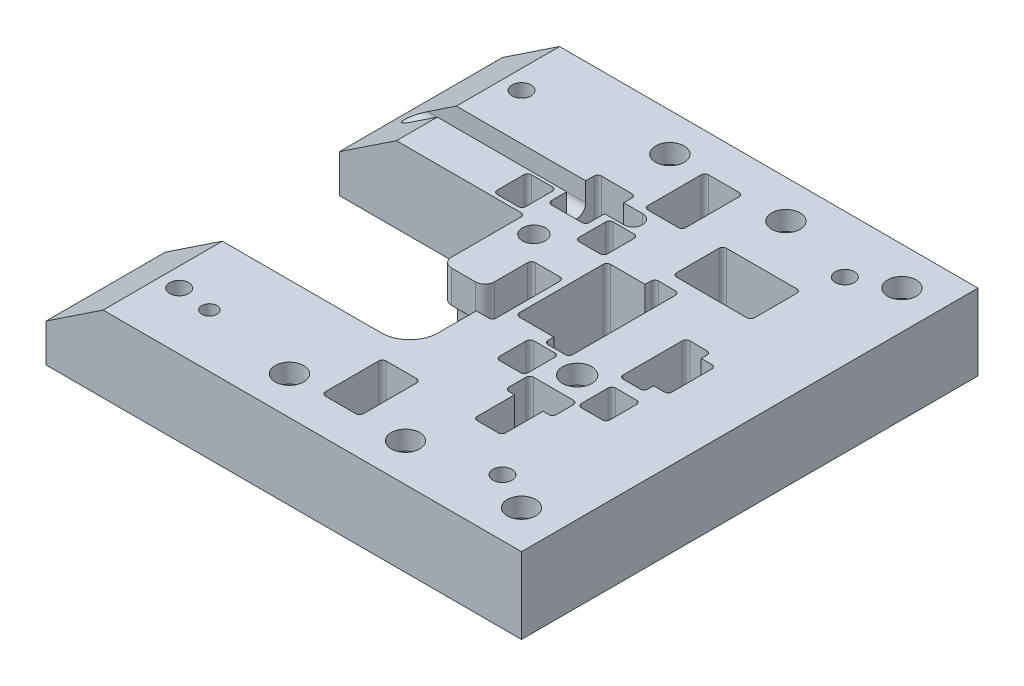
SolidWorks part; units mm, degrees
material "K110"
ref_plane "Front Plane" through (0, 0, 0) normal (0, 0, 1) x (1, 0, 0)
ref_plane "Top Plane" through (0, 0, 0) normal (0, 1, 0) x (1, 0, 0)
ref_plane "Right Plane" through (0, 0, 0) normal (1, 0, 0) x (0, 0, -1)
sketch "Sketch1" plane through (0, 0, 0) normal (0, 1, 0) x (1, 0, 0)
  line L1 (-125, -120) -> (125, -120)
  line L2 (-125, -120) -> (-125, 120)
  line L3 (-125, 120) -> (125, 120)
  line L4 (125, -120) -> (125, 120)
  line L5 (-125, -120) -> (125, 120) construction
  line L6 (-125, 120) -> (125, -120) construction
  point P0 (0, 0)
  dimension "D1" = 240
  dimension "D2" = 250
extrude "Boss-Extrude1" add sketch "Sketch1" along normal blind 40
sketch "Sketch2" plane through (0, 40, 0) normal (0, 1, 0) x (1, 0, 0)
  line L0 (40.25, 55.73) -> (78.25, 55.73) construction
  line L1 (38.75, 32.73) -> (38.75, -12.27) construction
  line L2 (81.25, 13.73) -> (81.25, -8.27) construction
  line L3 (53.25, -47.4) -> (65.25, -47.4) construction
  line L4 (40.25, 55.73) -> (78.25, 55.73)
  line L5 (38.75, 32.73) -> (38.75, -12.27)
  line L6 (81.25, 13.73) -> (81.25, -8.27)
  line L7 (53.25, -47.4) -> (65.25, -47.4)
sketch "Sketch3" plane through (0, 40, 0) normal (0, 1, 0) x (1, 0, 0)
  line L0 (53.25, -47.4) -> (65.25, -47.4) construction
  line L1 (51.75, -72.03) -> (66.75, -72.03)
  line L2 (51.75, -72.03) -> (51.75, -50.4)
  line L3 (46.75, -37.4) -> (71.75, -37.4)
  line L4 (66.75, -72.03) -> (66.75, -50.4)
  line L8 (59.25, -37.4) -> (59.25, -72.03) construction
  line L9 (59.25, 69.53) -> (59.25, -69.53) construction
  line L11 (66.75, -50.4) -> (71.75, -50.4)
  line L12 (71.75, -50.4) -> (71.75, -37.4)
  line L13 (51.75, -50.4) -> (46.75, -50.4)
  line L14 (46.75, -50.4) -> (46.75, -37.4)
  line L15 (89.38, -69.53) -> (18.13, -69.53) construction
  dimension "D1" = 10
  dimension "D2" = 15
  dimension "D3" = 3
  dimension "D4" = 25
  dimension "D5" = 2.5
extrude "Cut-Extrude2" cut sketch "Sketch3" against normal up to next contours L3 L12 L11 L4 L1 L2 L13 L14
fillet "Fillet3" radius 2 6 edges at (66.75, 20, 72.03) (51.75, 20, 72.03) (71.75, 20, 50.4) (46.75, 20, 50.4) (71.75, 20, 37.4) (46.75, 20, 37.4)
sketch "Sketch4" plane through (0, 40, 0) normal (0, 1, 0) x (1, 0, 0)
  line L0 (71.25, -14.77) -> (84.25, -14.77)
  line L5 (84.25, -14.77) -> (84.25, -9.77)
  line L6 (87.38, 13.73) -> (81.25, 13.73) construction
  line L7 (89.38, 69.53) -> (89.38, -69.53) construction
  line L8 (89.38, 2.73) -> (51.7072, 2.73) construction
  line L9 (89.38, -6.27) -> (89.38, 11.73) construction
  line L10 (84.25, -9.77) -> (91.88, -9.77)
  line L11 (91.88, -9.77) -> (91.88, 15.23)
  line L13 (91.88, 15.23) -> (84.25, 15.23)
  line L14 (84.25, 15.23) -> (84.25, 20.23)
  line L15 (84.25, 20.23) -> (71.25, 20.23)
  line L16 (71.25, 20.23) -> (71.25, -14.77)
  line L17 (81.25, 13.73) -> (81.25, -8.27) construction
  dimension "D1" = 1.5
  dimension "D2" = 5
  dimension "D3" = 2.5
  dimension "D4" = 10
  dimension "D5" = 3
extrude "Cut-Extrude3" cut sketch "Sketch4" against normal up to next
fillet "Fillet4" radius 2 6 edges at (91.88, 20, 9.77) (91.88, 20, -15.23) (84.25, 20, -20.23) (71.25, 20, -20.23) (71.25, 20, 14.77) (84.25, 20, 14.77)
sketch "Sketch5" plane through (0, 40, 0) normal (0, 1, 0) x (1, 0, 0)
  line L0 (15.63, -13.77) -> (35.75, -13.77)
  line L2 (35.75, -18.77) -> (48.75, -18.77)
  line L3 (48.75, -18.77) -> (48.75, 39.23)
  line L4 (48.75, 39.23) -> (35.75, 39.23)
  line L5 (35.75, 39.23) -> (35.75, 34.23)
  line L6 (35.75, 34.23) -> (15.63, 34.23)
  line L7 (15.63, 34.23) -> (15.63, -13.77)
  line L8 (38.75, 32.73) -> (38.75, -12.27) construction
  line L9 (18.13, 69.53) -> (18.13, -69.53) construction
  line L10 (18.13, 10.23) -> (48.75, 10.23) construction
  line L11 (18.13, 26.73) -> (18.13, -6.27) construction
  line L12 (35.75, -18.77) -> (35.75, -13.77)
  line L13 (24.13, -12.27) -> (38.75, -12.27) construction
  line L17 (5, -8.27) -> (5, 13.73) construction
  line L18 (5, 2.73) -> (-15, 2.73) construction
  dimension "D1" = 3
  dimension "D2" = 10
  dimension "D3" = 2.5
  dimension "D4" = 1.5
  dimension "D5" = 5
extrude "Cut-Extrude4" cut sketch "Sketch5" against normal up to next
fillet "Fillet5" radius 2 6 edges at (48.75, 20, -39.23) (35.75, 20, 18.77) (48.75, 20, 18.77) (15.63, 20, 13.77) (35.75, 20, -39.23) (15.63, 20, -34.23)
sketch "Sketch6" plane through (0, 40, 0) normal (0, 1, 0) x (1, 0, 0)
  line L0 (38.75, 72.03) -> (38.75, 45.73)
  line L3 (38.75, 45.73) -> (79.75, 45.73)
  line L6 (79.75, 45.73) -> (79.75, 72.03)
  line L7 (79.75, 72.03) -> (38.75, 72.03)
  line L8 (59.25, 69.53) -> (59.25, 45.73) construction
  line L9 (59.25, 69.53) -> (59.25, -69.53) construction
  line L10 (89.38, 69.53) -> (18.13, 69.53) construction
  line L12 (40.25, 55.73) -> (78.25, 55.73) construction
  dimension "D1" = 2.5
  dimension "D2" = 41
  dimension "D5" = 10
extrude "Cut-Extrude5" cut sketch "Sketch6" against normal up to next
fillet "Fillet6" radius 2 4 edges at (38.75, 20, -72.03) (79.75, 20, -72.03) (38.75, 20, -45.73) (79.75, 20, -45.73)
sketch "Sketch7" plane through (0, 40, 0) normal (0, 1, 0) x (1, 0, 0)
  line L0 (80.75, -29.77) -> (80.75, -32.27) construction
  line L3 (83.25, -29.77) -> (78.25, -29.77) construction
  line L4 (83.25, -27.27) -> (83.25, -32.27) construction
  line L5 (78.25, -11.27) -> (78.25, -38.4) construction
  line L7 (86.25, -20.77) -> (75.25, -20.77)
  line L8 (88.25, -22.77) -> (88.25, -36.77)
  line L9 (86.25, -38.77) -> (75.25, -38.77)
  line L10 (73.25, -22.77) -> (73.25, -36.77)
  arc A2 (75.25, -38.77) -> (73.25, -36.77) centre (75.25, -36.77) cw
  arc A3 (88.25, -36.77) -> (86.25, -38.77) centre (86.25, -36.77) cw
  arc A4 (86.25, -20.77) -> (88.25, -22.77) centre (86.25, -22.77) cw
  arc A5 (75.25, -20.77) -> (73.25, -22.77) centre (75.25, -22.77) ccw
  point P14 (73.25, -38.77)
  point P17 (88.25, -38.77)
  point P20 (88.25, -20.77)
  dimension "D4" = 2
  dimension "D1" = 2.5
  dimension "D2" = 18
  dimension "D3" = 15
  dimension "D5" = 9
extrude "Cut-Extrude6" cut sketch "Sketch7" against normal up to next
sketch "Sketch8" plane through (0, 40, 0) normal (0, 1, 0) x (1, 0, 0)
  line L0 (35.25, -29.77) -> (40.25, -29.77) construction
  line L3 (35.25, -32.27) -> (35.25, -27.27) construction
  line L4 (86.25, -20.77) -> (75.25, -20.77) construction
  line L7 (40.25, -38.4) -> (40.25, -13.77) construction
  line L8 (37.75, -29.77) -> (37.75, -32.27) construction
  line L9 (75.25, -38.77) -> (86.25, -38.77) construction
  line L10 (32.25, -20.77) -> (43.25, -20.77)
  line L11 (30.25, -22.77) -> (30.25, -36.77)
  line L12 (32.25, -38.77) -> (43.25, -38.77)
  line L13 (45.25, -22.77) -> (45.25, -36.77)
  arc A2 (30.25, -36.77) -> (32.25, -38.77) centre (32.25, -36.77) ccw
  arc A3 (43.25, -38.77) -> (45.25, -36.77) centre (43.25, -36.77) ccw
  arc A4 (43.25, -20.77) -> (45.25, -22.77) centre (43.25, -22.77) cw
  arc A5 (32.25, -20.77) -> (30.25, -22.77) centre (32.25, -22.77) ccw
  dimension "D1" = 2.5
  dimension "D2" = 2
extrude "Cut-Extrude7" cut sketch "Sketch8" against normal up to next
sketch "Sketch21" plane through (0, 40, 0) normal (0, 1, 0) x (1, 0, 0)
  line L0 (2, 55.73) -> (2, 16.73) construction
  line L3 (-1, 54.23) -> (10, 54.23)
  line L4 (-3, 52.23) -> (-3, 38.23)
  line L5 (-1, 36.23) -> (10, 36.23)
  line L6 (12, 52.23) -> (12, 38.23)
  line L7 (2, 55.73) -> (-36, 55.73) construction
  line L9 (7, 45.23) -> (2, 45.23) construction
  line L10 (4.5, 45.23) -> (4.5, 54.23) construction
  line L11 (-17, 55.73) -> (-17, 36.23) construction
  line L12 (7, 42.73) -> (7, 47.73) construction
  line L16 (-46, 52.23) -> (-46, 38.23)
  line L17 (-33, 36.23) -> (-44, 36.23)
  line L18 (-31, 52.23) -> (-31, 38.23)
  line L19 (-33, 54.23) -> (-44, 54.23)
  arc A2 (-3, 38.23) -> (-1, 36.23) centre (-1, 38.23) ccw
  arc A3 (10, 36.23) -> (12, 38.23) centre (10, 38.23) ccw
  arc A4 (10, 54.23) -> (12, 52.23) centre (10, 52.23) cw
  arc A5 (-1, 54.23) -> (-3, 52.23) centre (-1, 52.23) ccw
  arc A6 (-33, 54.23) -> (-31, 52.23) centre (-33, 52.23) cw
  arc A7 (-44, 54.23) -> (-46, 52.23) centre (-44, 52.23) ccw
  arc A8 (-44, 36.23) -> (-46, 38.23) centre (-44, 38.23) cw
  arc A9 (-31, 38.23) -> (-33, 36.23) centre (-33, 38.23) cw
  dimension "D4" = 15
  dimension "D2" = 2
  dimension "D1" = 2.5
  dimension "D3" = 18
extrude "Cut-Extrude12" cut sketch "Sketch21" against normal up to next
sketch "Sketch22" plane through (0, 40, 0) normal (0, 1, 0) x (1, 0, 0)
  line L0 (-125, 120) -> (-125, -120) construction
  line L1 (-125, 55.73) -> (8, 55.73)
  line L2 (-125, 55.73) -> (-125, 65.726)
  line L3 (-125, 65.726) -> (8, 65.726)
  line L4 (8, 55.73) -> (8, 65.726)
  line L5 (2, 55.73) -> (-36, 55.73) construction
  line L6 (-36, 63.776) -> (2, 63.776) construction
  line L7 (2, 55.73) -> (2, 61.5256) construction
  line L8 (8, 60.728) -> (-125, 60.728) construction
  dimension "D1" = 1.95
  dimension "D2" = 6
ref_plane "Plane1" through (0, 0, -60.728) normal (0, 0, -1) x (-1, 0, 0)
sketch "Sketch24" plane through (0, 0, -60.728) normal (0, 0, -1) x (-1, 0, 0)
  line L0 (-8, 40) -> (-8, 35)
  line L1 (-8, 40) -> (125, 40) construction
  line L2 (2, 25) -> (125, 25)
  line L3 (125, 40) -> (125, 0) construction
  line L4 (-8, 40) -> (125, 40)
  line L5 (125, 40) -> (125, 25)
  arc A0 (-8, 35) -> (2, 25) centre (2, 35) ccw
  dimension "D2" = 10
  dimension "D1" = 15
extrude "Cut-Extrude15" cut sketch "Sketch24" against normal mid plane 10
fillet "Fillet9" 2 edges at (-63.5, 25, -55.728) (-63.5, 25, -65.728) type full round first side face at (-46.7858, 32.5858, -55.728) second side face at (-46.7858, 32.5858, -65.728) middle face at (-63.5, 25, -60.728)
sketch "Sketch23" plane through (0, 40, 0) normal (0, 1, 0) x (1, 0, 0)
  line L0 (-17, 55.73) -> (-17, 45.73) construction
  line L1 (-25, 72.03) -> (-9, 72.03)
  line L2 (-27, 70.03) -> (-27, 47.73)
  line L3 (-25, 45.73) -> (-9, 45.73)
  line L4 (-7, 70.03) -> (-7, 47.73)
  line L5 (2, 55.73) -> (-36, 55.73) construction
  line L6 (40.75, 45.73) -> (77.75, 45.73) construction
  line L7 (77.75, 72.03) -> (40.75, 72.03) construction
  arc A0 (-27, 47.73) -> (-25, 45.73) centre (-25, 47.73) ccw
  arc A1 (-25, 72.03) -> (-27, 70.03) centre (-25, 70.03) ccw
  arc A2 (-9, 72.03) -> (-7, 70.03) centre (-9, 70.03) cw
  arc A3 (-9, 45.73) -> (-7, 47.73) centre (-9, 47.73) ccw
  point P14 (-27, 45.73)
  point P21 (-7, 45.73)
  dimension "D2" = 2
  dimension "D1" = 20
extrude "Cut-Extrude14" cut sketch "Sketch23" against normal up to next
sketch "Sketch26" plane through (0, 40, 0) normal (0, 1, 0) x (1, 0, 0)
  line L0 (-125, 55.728) -> (-125, -120) construction
  line L1 (-125, 34.23) -> (-27.5, 34.23)
  line L2 (-125, 34.23) -> (-125, -57.27)
  line L3 (-125, -57.27) -> (3.5, -57.27)
  line L4 (3.5, -22.27) -> (3.5, -57.27)
  line L5 (-37.5, 32.73) -> (-43.5, 32.73) construction
  line L6 (-27.5, 34.23) -> (-27.5, -9.27)
  line L7 (-27.5, -9.27) -> (-5, -9.27)
  line L8 (-36, -19.27) -> (2, -19.27) construction
  line L9 (2, -11.27) -> (2, -19.27) construction
  line L10 (-5, -9.27) -> (-5, 15.23)
  line L11 (-37.5, -12.27) -> (-37.5, 32.73) construction
  line L12 (3.5, -22.27) -> (12, -22.27)
  line L13 (12, -22.27) -> (12, 15.23)
  line L14 (-5, 15.23) -> (12, 15.23)
  line L15 (5, -8.27) -> (5, 13.73) construction
  line L16 (11, 13.73) -> (5, 13.73) construction
  dimension "D1" = 1.5
  dimension "D2" = 10
  dimension "D3" = 1.5
  dimension "D4" = 35
  dimension "D5" = 10
  dimension "D6" = 1.5
  dimension "D7" = 3
  dimension "D8" = 10
  dimension "D9" = 7
extrude "Cut-Extrude16" cut sketch "Sketch26" against normal up to next contours L1 L6 L7 L10 L14 L13 L12 L4 L3 L2
fillet "Fillet10" radius 2 4 edges at (12, 20, 22.27) (-27.5, 20, -34.23) (12, 20, -15.23) (-5, 20, -15.23)
sketch "Sketch27" plane through (-27.5, 0, 0) normal (-1, 0, 0) x (0, 0, 1)
  line L0 (-32.23, 0) -> (9.27, 0) construction
  line L1 (1.27, 0) -> (9.27, 0)
  line L2 (1.27, 0) -> (1.27, 23)
  line L3 (1.27, 23) -> (9.27, 23)
  line L4 (9.27, 0) -> (9.27, 23)
  line L5 (9.27, 23) -> (9.27, 0) construction
  dimension "D1" = 23
  dimension "D2" = 8
extrude "Cut-Extrude17" cut sketch "Sketch27" against normal blind 18.5 contours L4 L3 L2 L1
fillet "Fillet11" radius 3 3 edges at (-9, 23, 5.27) (-18.25, 23, 1.27) (-9, 11.5, 1.27)
fillet "Fillet12" radius 15 1 edges at (3.5, 20, 57.27)
fillet "Fillet13" radius 5 2 edges at (-27.5, 31.5, 9.27) (-5, 20, 9.27)
chamfer "Chamfer1" distance 20 distance2 30 2 edges at (-125, 40, -44.979) (-125, 40, 88.635) first distance on face at (-125, 26.875, -68.9215) first distance on face at (-125, 20, 88.635)
sketch "Sketch28" plane through (0, 40, 0) normal (0, 1, 0) x (1, 0, 0)
  line L0 (8.13, 84.765) -> (13.13, 84.765) construction
  line L1 (2.63, 100.765) -> (18.63, 100.765)
  line L2 (0.63, 98.765) -> (0.63, 70.765)
  line L3 (2.63, 68.765) -> (18.63, 68.765)
  line L4 (20.63, 98.765) -> (20.63, 70.765)
  line L5 (8.13, 95) -> (8.13, 74.53) construction
  line L6 (13.13, 50.73) -> (13.13, 95) construction
  line L7 (10.63, 84.765) -> (10.63, 95.765) construction
  line L8 (10.63, 95.765) -> (10.63, 73.765) construction
  line L9 (13.36, 95.765) -> (13.36, 73.765) construction
  line L10 (7.9, 95.765) -> (7.9, 73.765) construction
  arc A0 (13.36, 95.765) -> (7.9, 95.765) centre (10.63, 95.765) ccw construction
  arc A1 (7.9, 73.765) -> (13.36, 73.765) centre (10.63, 73.765) ccw construction
  arc A2 (0.63, 70.765) -> (2.63, 68.765) centre (2.63, 70.765) ccw
  arc A3 (18.63, 68.765) -> (20.63, 70.765) centre (18.63, 70.765) ccw
  arc A4 (18.63, 100.765) -> (20.63, 98.765) centre (18.63, 98.765) cw
  arc A5 (2.63, 100.765) -> (0.63, 98.765) centre (2.63, 98.765) ccw
  point P12 (10.63, 84.765)
  point P26 (20.63, 68.765)
  point P29 (20.63, 100.765)
  point P32 (0.63, 100.765)
  dimension "D4" = 2.73
  dimension "D5" = 2
  dimension "D1" = 32
  dimension "D2" = 20
  dimension "D3" = 22
extrude "Cut-Extrude18" cut sketch "Sketch28" against normal up to next
mirror "Mirror1" about plane through (0, 0, 0) normal (0, 0, 1) of "Cut-Extrude18"
sketch "Sketch30" plane through (0, 40, 0) normal (0, 1, 0) x (1, 0, 0)
  line L1 (48.75, -37.4) -> (69.75, -37.4) construction
  line L2 (-22, 0) -> (22, 0) construction
  circle A0 centre (59.25, -25) radius 7.6846
  point P5 (59.25, -37.4)
  dimension "D1" = 25
extrude "Cut-Extrude19" cut sketch "Sketch30" against normal up to next
sketch "Sketch31" plane through (0, 0, 0) normal (0, -1, 0) x (1, 0, 0)
  circle A0 centre (59.25, 25) radius 10
  dimension "D1" = 20
extrude "Cut-Extrude20" cut sketch "Sketch31" against normal blind 30
sketch "Sketch33" plane through (0, 40, 0) normal (0, 1, 0) x (1, 0, 0)
  line L0 (-16.25, -9.27) -> (-16.25, 45.73) construction
  line L1 (-22.5, -9.27) -> (-10, -9.27) construction
  line L2 (-25, 45.73) -> (-9, 45.73) construction
  line L3 (-3, 15.23) -> (10, 15.23) construction
  circle A0 centre (-16.25, 27.73) radius 6
  dimension "D1" = 12
  dimension "D2" = 12.5
extrude "Cut-Extrude21" cut sketch "Sketch33" against normal up to next contours A0
sketch "Sketch34" plane through (0, 0, 0) normal (0, -1, 0) x (1, 0, 0)
  circle A0 centre (-16.25, -27.73) radius 9
  dimension "D1" = 18
extrude "Cut-Extrude22" cut sketch "Sketch34" against normal blind 31
hole_wizard "M10 Tapped Hole1" positions "Sketch45" profile "Sketch36" tap size "M10" standard "ISO"
sketch "Sketch45" plane through (0, 0, 0) normal (0, -1, 0) x (-1, 0, 0)
  line L0 (-125, 120) -> (125, 120) construction
  line L1 (-125, -120) -> (-125, 120) construction
  line L2 (125, 120) -> (125, 34.23) construction
  line L3 (125, -120) -> (-125, -120) construction
  point P0 (-85, 107.5)
  point P2 (85, 107.5)
  point P4 (85, -107.5)
  point P6 (-85, -107.5)
  dimension "D1" = 12.5
  dimension "D2" = 40
  dimension "D3" = 40
  dimension "D4" = 12.5
sketch "Sketch36" plane through (85, 0, -107.5) normal (1, 0, 0) x (0, 0, -1)
  line L0 (0, 0) -> (0, 30.0537)
  line L1 (0, 30.0537) -> (4.25, 27.5)
  line L2 (4.25, 27.5) -> (4.25, 0.775)
  line L3 (4.25, 0.775) -> (5.025, 0)
  line L5 (5.025, 0) -> (0, 0)
  line L6 (-4.25, 0.775) -> (-5.025, 0) construction
  line L10 (0, 30.0537) -> (-4.25, 27.5) construction
  line L11 (0, -6.35) -> (0, 107.95) construction
  dimension "Tap Drill Dia." = 8.5
  dimension "Tap Drill Depth" = 27.5
  dimension "Near C'Sink Dia." = 10.05
  dimension "Near C'Sink Angle" = 90
  dimension "Drill Angle" = 118
cosmetic thread "Hole Thread1" parameters "D1"=20, "D2"=10
cosmetic thread "Hole Thread2" parameters "D1"=20, "D2"=10
cosmetic thread "Hole Thread3" parameters "D1"=20, "D2"=10
cosmetic thread "Hole Thread4" parameters "D1"=20, "D2"=10
hole_wizard "Ø10.0mm Dowel Hole1" positions "Sketch46" profile "Sketch39" hole size "Ø10.0" standard "ISO" end condition through all
sketch "Sketch46" plane through (0, 0, 0) normal (0, -1, 0) x (-1, 0, 0)
  line L0 (-125, -120) -> (-125, 120) construction
  line L1 (125, 120) -> (125, 34.23) construction
  circle A0 centre (-85, 107.5) radius 4.25 construction
  circle A1 centre (-85, -107.5) radius 4.25 construction
  point P0 (-85, 90)
  point P2 (85, 90)
  point P4 (85, -90)
  point P6 (-85, -90)
  dimension "D4" = 17.5
  dimension "D1" = 17.5
  dimension "D2" = 40
  dimension "D3" = 40
sketch "Sketch39" plane through (85, 0, -90) normal (1, 0, 0) x (0, 0, -1)
  line L0 (0, 0) -> (0, 40)
  line L1 (0, 40) -> (5, 40)
  line L2 (5, 40) -> (5, 0)
  line L5 (5, 0) -> (0, 0)
  line L11 (0, -6.35) -> (0, 107.95) construction
  dimension "Thru Hole Dia." = 10
  dimension "Thru Hole Depth" = 40
sketch "Sketch41" plane through (0, 40, 0) normal (0, 1, 0) x (1, 0, 0)
  line L0 (13.13, -95) -> (475.63, -95) construction
  line L1 (125, -120) -> (125, 120) construction
  line L2 (-17, -19.27) -> (-17, -100) construction
  line L3 (-22, 0) -> (22, 0) construction
  line L4 (2, -19.27) -> (-36, -19.27) construction
  circle A0 centre (105, -100) radius 7.5
  circle A1 centre (44, -100) radius 7.5
  circle A2 centre (105, 100) radius 7.5
  circle A3 centre (44, 100) radius 7.5
  circle A4 centre (-17, -100) radius 7.5
  circle A5 centre (-17, 100) radius 7.5
  dimension "D2" = 15
  dimension "D1" = 5
  dimension "D3" = 61
  dimension "D4" = 20
  dimension "D5" = 122
extrude "Cut-Extrude23" cut sketch "Sketch41" against normal up to next
sketch "Sketch42" plane through (0, 0, 0) normal (0, -1, 0) x (1, 0, 0)
  circle A0 centre (105, 100) radius 9
  circle A1 centre (44, 100) radius 9
  circle A2 centre (105, -100) radius 9
  circle A3 centre (44, -100) radius 9
  circle A4 centre (-17, 100) radius 9
  circle A5 centre (-17, -100) radius 9
  dimension "D1" = 18
extrude "Cut-Extrude24" cut sketch "Sketch42" against normal blind 30
sketch "Sketch47" plane through (0, 40, 0) normal (0, 1, 0) x (1, 0, 0)
  line L0 (-63.12, -27.27) -> (-63.12, -95) construction
  line L1 (-63.12, -95) -> (8.13, -95) construction
  circle A0 centre (-67.12, -92) radius 4
  dimension "D2" = 8
  dimension "D1" = 3
extrude "Cut-Extrude25" cut sketch "Sketch47" against normal blind 20
